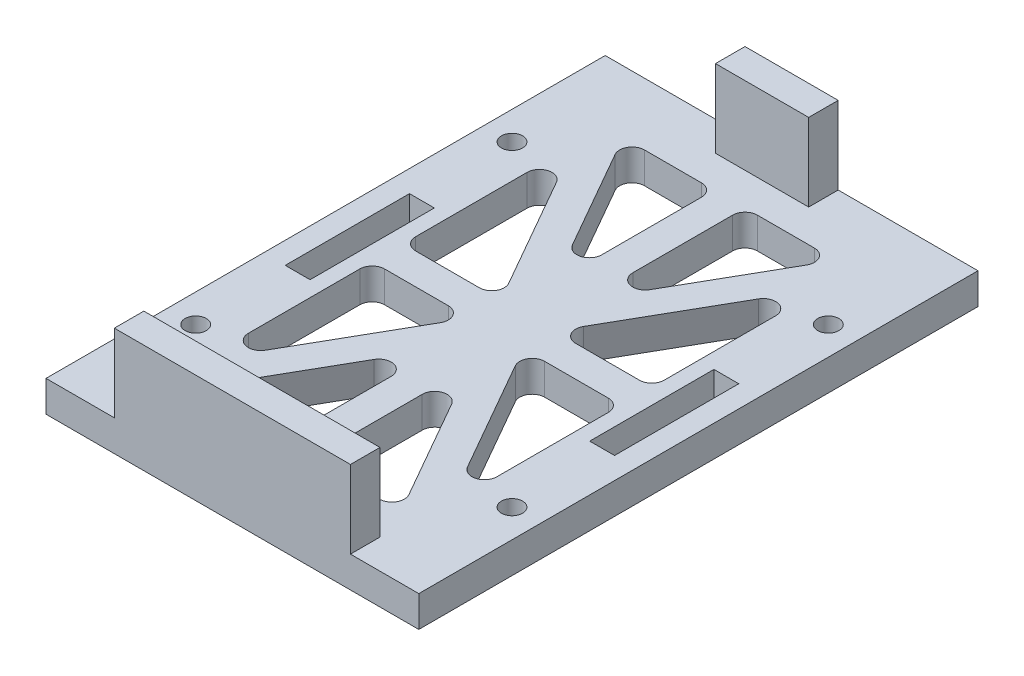
SolidWorks part; units mm, degrees
ref_plane "Front Plane" through (0, 0, 0) normal (0, 0, 1) x (1, 0, 0)
ref_plane "Top Plane" through (0, 0, 0) normal (0, 1, 0) x (1, 0, 0)
ref_plane "Right Plane" through (0, 0, 0) normal (1, 0, 0) x (0, 0, -1)
sketch "Sketch2" plane through (0, 0, 0) normal (0, 1, 0) x (1, 0, 0)
  line L0 (-30, 0) -> (-19, 0) construction
  line L1 (-30, -45) -> (30, -45)
  line L2 (-30, -45) -> (-30, 45)
  line L3 (-30, 45) -> (30, 45)
  line L4 (30, -45) -> (30, 45)
  line L5 (-30, -45) -> (30, 45) construction
  line L6 (-30, 45) -> (30, -45) construction
  line L7 (-19, -39.5) -> (19, -39.5) construction
  line L8 (-19, -39.5) -> (-19, 39.5) construction
  line L9 (-19, 39.5) -> (19, 39.5) construction
  line L10 (19, -39.5) -> (19, 39.5) construction
  line L11 (-19, -39.5) -> (19, 39.5) construction
  line L12 (-19, 39.5) -> (19, -39.5) construction
  line L13 (-26.5, 10) -> (-22.5, 10)
  line L14 (-26.5, 10) -> (-26.5, -10)
  line L15 (-26.5, -10) -> (-22.5, -10)
  line L16 (-22.5, 10) -> (-22.5, -10)
  line L17 (0, -55) -> (0, 55) construction
  line L18 (26.5, -10) -> (22.5, -10)
  line L19 (22.5, 10) -> (22.5, -10)
  line L20 (26.5, 10) -> (22.5, 10)
  line L21 (26.5, 10) -> (26.5, -10)
  point P0 (0, 0)
  point P6 (0, 0)
  point P15 (-19, 0)
  point P16 (-22.5, 0)
  point P19 (-24.5, 0)
  point P20 (-24.5, 10)
  dimension "D1" = 60
  dimension "D2" = 90
  dimension "D3" = 79
  dimension "D4" = 38
  dimension "D5" = 20
  dimension "D6" = 4
extrude "Boss-Extrude1" add sketch "Sketch2" along normal mid plane 5
hole_wizard "M3 Clearance Hole2" positions "Sketch10" profile "Sketch11" hole size "M3" standard "ANSI Metric" end condition up to next
sketch "Sketch10" plane through (0, 2.5, 0) normal (0, 1, 0) x (1, 0, 0)
  line L8 (-67.8823, 0) -> (0, 67.8823) construction
  line L9 (-67.8823, 0) -> (0, -67.8823) construction
  line L10 (0, 67.8823) -> (67.8823, 0) construction
  line L11 (0, -67.8823) -> (67.8823, 0) construction
  line L12 (-67.8823, 0) -> (67.8823, 0) construction
  line L13 (0, 67.8823) -> (0, -67.8823) construction
  line L14 (30, 45) -> (-30, 45) construction
  line L15 (33.9411, -33.9411) -> (25.4558, -25.4558) construction
  line L17 (-33.9411, -33.9411) -> (-25.4558, -25.4558) construction
  line L18 (-33.9411, 33.9411) -> (-25.4558, 25.4558) construction
  line L19 (33.9411, 33.9411) -> (25.4558, 25.4558) construction
  point P317 (25.4558, -25.4558)
  point P341 (-33.9411, -33.9411)
  point P345 (-25.4558, -25.4558)
  point P348 (-25.4558, 25.4558)
  point P351 (25.4558, 25.4558)
  point P357 (0, 0)
  dimension "D1" = 96
  dimension "D2" = 12
  dimension "D3" = 4
sketch "Sketch11" plane through (25.4558, 2.5, -25.4558) normal (1, 0, 0) x (0, 0, 1)
  line L0 (0, 0) -> (0, 5)
  line L1 (0, 5) -> (1.7, 5)
  line L2 (1.7, 5) -> (1.7, 0)
  line L5 (1.7, 0) -> (0, 0)
  line L11 (0, -6.35) -> (0, 107.95) construction
  dimension "Thru Hole Dia." = 3.4
  dimension "Thru Hole Depth" = 5
sketch "Sketch12" plane through (0, 2.5, 0) normal (0, 1, 0) x (1, 0, 0)
  line L0 (-30, -45) -> (30, -45) construction
  line L1 (-19, -40.25) -> (19, -40.25) construction
  line L2 (-19, -40.25) -> (-19, 40.25) construction
  line L3 (-19, 40.25) -> (19, 40.25) construction
  line L4 (19, -40.25) -> (19, 40.25) construction
  line L5 (-19, -40.25) -> (19, 40.25) construction
  line L6 (-19, 40.25) -> (19, -40.25) construction
  line L7 (-19, -40.25) -> (19, -40.25)
  line L8 (-19, -40.25) -> (-19, -45)
  line L9 (-19, -45) -> (19, -45)
  line L10 (19, -40.25) -> (19, -45)
  line L11 (30, 45) -> (-30, 45) construction
  line L12 (-7.5, 40.25) -> (7.5, 40.25)
  line L13 (-7.5, 40.25) -> (-7.5, 45)
  line L14 (-7.5, 45) -> (7.5, 45)
  line L15 (7.5, 40.25) -> (7.5, 45)
  point P0 (0, 0)
  point P16 (0, 40.25)
  dimension "D1" = 38
  dimension "D2" = 80.5
  dimension "D3" = 15
extrude "Boss-Extrude4" add sketch "Sketch12" along normal blind 12.5
sketch "Sketch13" plane through (0, 2.5, 0) normal (0, 1, 0) x (1, 0, 0)
  line L0 (-7.5, 45) -> (-30, 45) construction
  line L1 (20, -35) -> (-20, -35)
  line L2 (20, -35) -> (20, 35)
  line L3 (20, 35) -> (-20, 35)
  line L4 (-20, -35) -> (-20, 35)
  line L5 (20, -35) -> (-20, 35) construction
  line L6 (20, 35) -> (-20, -35) construction
  line L7 (-30, 45) -> (-30, -45) construction
  line L8 (20, -29.9611) -> (-17.1206, 35)
  line L9 (-20, 29.9611) -> (17.1206, -35)
  line L10 (-17.1206, -35) -> (20, 29.9611)
  line L11 (17.1206, 35) -> (-20, -29.9611)
  line L13 (20, -2.5) -> (-20, -2.5)
  line L14 (20, -2.5) -> (20, 2.5)
  line L15 (20, 2.5) -> (-20, 2.5)
  line L16 (-20, -2.5) -> (-20, 2.5)
  line L17 (20, -2.5) -> (-20, 2.5) construction
  line L18 (20, 2.5) -> (-20, -2.5) construction
  line L19 (2.5, -35) -> (-2.5, -35)
  line L20 (2.5, -35) -> (2.5, 35)
  line L21 (2.5, 35) -> (-2.5, 35)
  line L22 (-2.5, -35) -> (-2.5, 35)
  line L23 (2.5, -35) -> (-2.5, 35) construction
  line L24 (2.5, 35) -> (-2.5, -35) construction
  point P0 (0, 0)
  point P18 (0, 0)
  point P23 (0, 0)
  dimension "D1" = 10
  dimension "D2" = 10
  dimension "D3" = 5
  dimension "D4" = 5
  dimension "D5" = 5
extrude "Cut-Extrude1" cut sketch "Sketch13" against normal up to next contours L1 L22 L10 | L11 L13 L4 | L15 L9 L4 | L8 L22 L3 | L20 L11 L3 | L15 L2 L10 | L2 L13 L8 | L20 L1 L9 region at (7.3735, 2.5, 26.4713) region at (14.7693, 2.5, 11.6537) region at (-7.3735, 2.5, 26.4713) region at (14.7693, 2.5, -11.6537) region at (-14.7693, 2.5, 11.6537) region at (7.3735, 2.5, -26.4713) region at (-14.7693, 2.5, -11.6537) region at (-7.3735, 2.5, -26.4713)
fillet "Fillet1" radius 2 24 edges at (2.5, 0, 9.4139) (2.5, 0, 35) (17.1206, 0, 35) (20, 0, 29.9611) (20, 0, 2.5) (4.3079, 0, 2.5) (4.3079, 0, -2.5) (20, 0, -2.5) (20, 0, -29.9611) (17.1206, 0, -35) (2.5, 0, -35) (2.5, 0, -9.4139) (-2.5, 0, -9.4139) (-2.5, 0, -35) (-17.1206, 0, -35) (-20, 0, -29.9611) (-4.3079, 0, -2.5) (-20, 0, -2.5) (-20, 0, 29.9611) (-20, 0, 2.5) (-4.3079, 0, 2.5) (-2.5, 0, 9.4139) (-2.5, 0, 35) (-17.1206, 0, 35)
